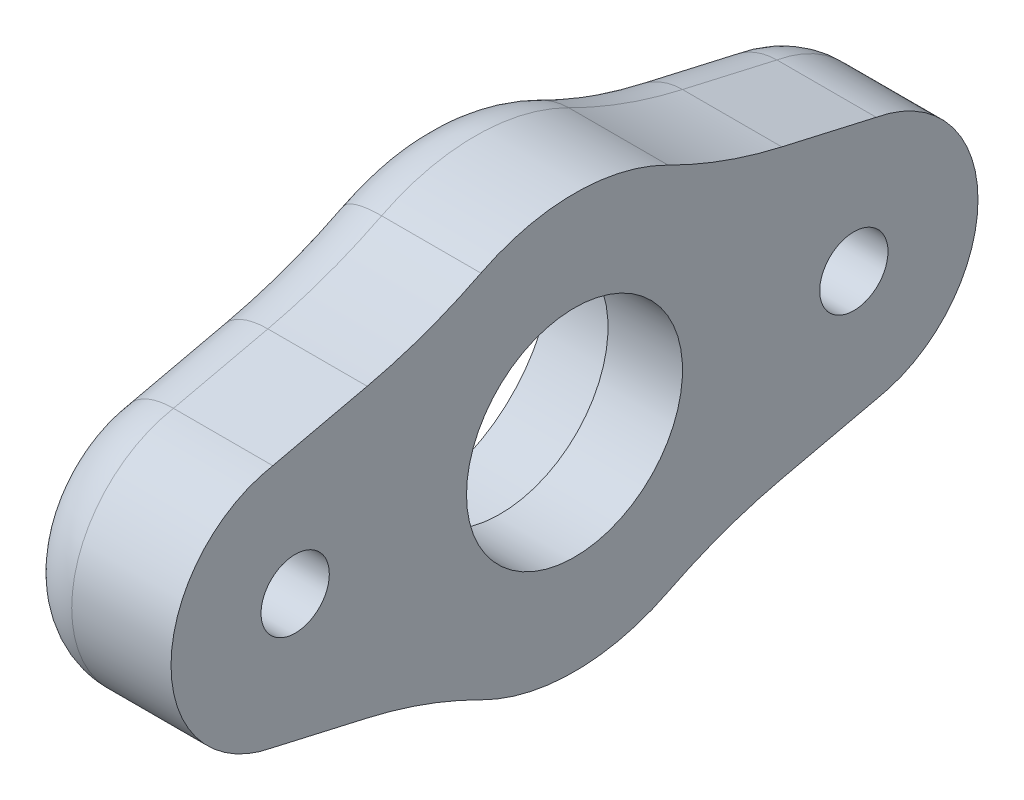
SolidWorks part; units mm, degrees
ref_plane "Ebene vorne" through (0, 0, 0) normal (0, 0, 1) x (1, 0, 0)
ref_plane "Ebene oben" through (0, 0, 0) normal (0, 1, 0) x (1, 0, 0)
ref_plane "Ebene rechts" through (0, 0, 0) normal (1, 0, 0) x (0, 0, -1)
sketch "Skizze4" plane through (0, 0, 0) normal (0, 0, 1) x (1, 0, 0)
  line L0 (0, 11.2) -> (7, 11.2)
  line L1 (0, 11.2) -> (0, 16.6831)
  line L2 (0, 16.6831) -> (13, 16.6831)
  line L3 (13, 16.6831) -> (13, 8.7)
  line L4 (13, 8.7) -> (7, 8.7)
  line L5 (7, 8.7) -> (7, 11.2)
  line L6 (0, 0) -> (13.1594, 0) construction
  dimension "D1" = 11.2
  dimension "D2" = 7
  dimension "D3" = 2.5
  dimension "D4" = 6
revolve "Rotation1" add sketch "Skizze4" angle 360 about L6
sketch "Skizze5" plane through (13, 0, 0) normal (1, 0, 0) x (0, 0, -1)
  line L0 (-22.5, 0) -> (22.5, 0) construction
  line L1 (-22.5, 0) -> (22.5, 0) construction
  line L2 (-24.3035, 9.836) -> (-10.4558, 13)
  line L4 (-24.3035, -9.836) -> (-10.4558, -13)
  arc A3 (-24.3035, 9.836) -> (-24.3035, -9.836) centre (-22.5, 0) ccw
  arc A5 (-10.4558, 13) -> (-10.4558, -13) centre (0, 0) ccw
  circle A6 centre (0, 0) radius 16.6831 construction
  arc A7 (3.7725, 16.2509) -> (-1.9378, -16.5701) centre (0, 0) ccw
  point P0 (0, 0)
  point P4 (0, 0)
  point P6 (-10.7767, -12.9267)
  point P16 (-22.5, 0)
  dimension "D2" = 10
  dimension "D3" = 13
  dimension "D1" = 45
extrude "Aufsatz-Linear austragen1" add sketch "Skizze5" against normal blind 13 contours A5 L4 A3 L2
hole_wizard "Ø5.5 (5.5) Durchmesser Bohrung1" positions "Skizze6" profile "Skizze7" hole size "Ø5.5" standard "ISO" end condition through all
sketch "Skizze6" plane through (13, 0, 0) normal (1, 0, 0) x (0, 0, -1)
  point P0 (-22.5, 0)
sketch "Skizze7" plane through (13, 0, 22.5) normal (0, 1, 0) x (0, 0, -1)
  line L0 (0, 0) -> (0, 13)
  line L1 (0, 13) -> (2.75, 13)
  line L2 (2.75, 13) -> (2.75, 0)
  line L5 (2.75, 0) -> (0, 0)
  line L11 (0, -6.35) -> (0, 107.95) construction
  dimension "Bohrerdurchmesser" = 5.5
  dimension "Bohrungstiefe" = 13
mirror "Spiegeln1" about plane through (0, 0, 0) normal (0, 0, 1) of "Ø5.5 (5.5) Durchmesser Bohrung1", "Aufsatz-Linear austragen1"
fillet "Verrundung2" radius 40 4 edges at (6.5, 13, 10.4558) (6.5, 13, -10.4558) (6.5, -13, -10.4558) (6.5, -13, 10.4558)
fillet "Verrundung3" radius 5 12 edges at (0, -12.9487, 12.0164) (0, -12.9487, -12.0164) (0, -10.7049, -20.5008) (0, -16.6831, 0) (0, 10.7049, 20.5008) (0, 12.9487, 12.0164) (0, -10.7049, 20.5008) (0, 0, 32.5) (0, 0, -32.5) (0, 10.7049, -20.5008) (0, 12.9487, -12.0164) (0, 16.6831, 0)
